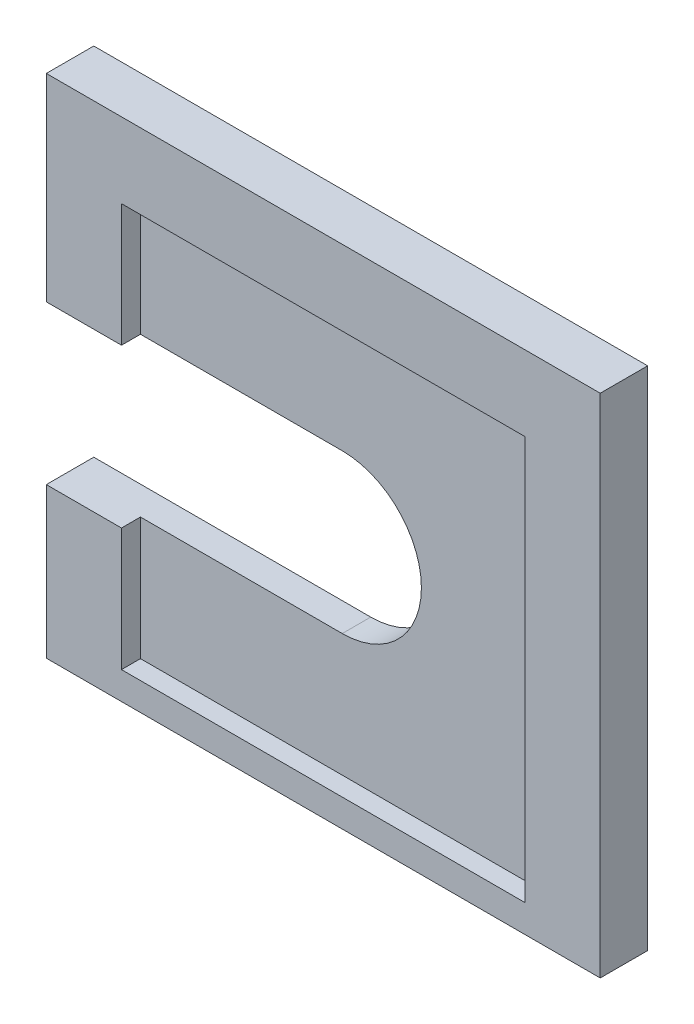
SolidWorks part; units mm, degrees
ref_plane "Front Plane" through (0, 0, 0) normal (0, 0, 1) x (1, 0, 0)
ref_plane "Top Plane" through (0, 0, 0) normal (0, 1, 0) x (1, 0, 0)
ref_plane "Right Plane" through (0, 0, 0) normal (1, 0, 0) x (0, 0, -1)
sketch "Sketch1" plane through (0, 0, 0) normal (0, 0, 1) x (1, 0, 0)
  line L1 (0, 0) -> (35, 0)
  line L2 (0, 0) -> (0, 35)
  line L3 (0, 35) -> (35, 35)
  line L4 (35, 0) -> (35, 35)
  dimension "D1" = 35
  dimension "D2" = 35
extrude "Boss-Extrude1" add sketch "Sketch1" along normal blind 3
sketch "Sketch2" plane through (0, 0, 3) normal (0, 0, 1) x (1, 0, 0)
  line L0 (17.5, 30.25) -> (17.5, 17.5) construction
  line L1 (4.75, 30.25) -> (30.25, 30.25)
  line L2 (4.75, 30.25) -> (4.75, 4.75)
  line L3 (4.75, 4.75) -> (30.25, 4.75)
  line L4 (30.25, 30.25) -> (30.25, 4.75)
  line L5 (17.5, 17.5) -> (4.75, 17.5) construction
  line L8 (17.5, 35) -> (17.5, 17.5) construction
  line L9 (35, 35) -> (0, 35) construction
  line L10 (17.5, 17.5) -> (35, 17.5) construction
  line L11 (35, 0) -> (35, 35) construction
  dimension "D1" = 25.5
  dimension "D2" = 25.5
extrude "Cut-Extrude1" cut sketch "Sketch2" against normal blind 1.2
sketch "Sketch3" plane through (0, 0, 0) normal (0, -1, 0) x (1, 0, 0)
  line L4 (0, 0) -> (35, 0)
  line L5 (35, 0) -> (35, 3)
  line L6 (35, 3) -> (0, 3)
  line L7 (0, 3) -> (0, 0)
  line L8 (0, 0) -> (35, 0)
  line L9 (35, 0) -> (35, 3)
  line L10 (35, 3) -> (0, 3)
  line L11 (0, 3) -> (0, 0)
  dimension "D1" = 0
extrude "Cut-Extrude2" cut sketch "Sketch3" against normal blind 3
sketch "Sketch5" plane through (0, 0, 0) normal (0, 0, -1) x (-1, 0, 0)
  line L0 (-17.5, 12.5) -> (0, 12.5)
  line L1 (0, 35) -> (0, 3) construction
  line L2 (0, 12.5) -> (0, 22.5)
  line L3 (0, 22.5) -> (-17.5, 22.5)
  arc A0 (-17.5, 22.5) -> (-17.5, 12.5) centre (-17.5, 17.5) ccw
  dimension "D1" = 10
extrude "Cut-Extrude3" cut sketch "Sketch5" against normal up to next
